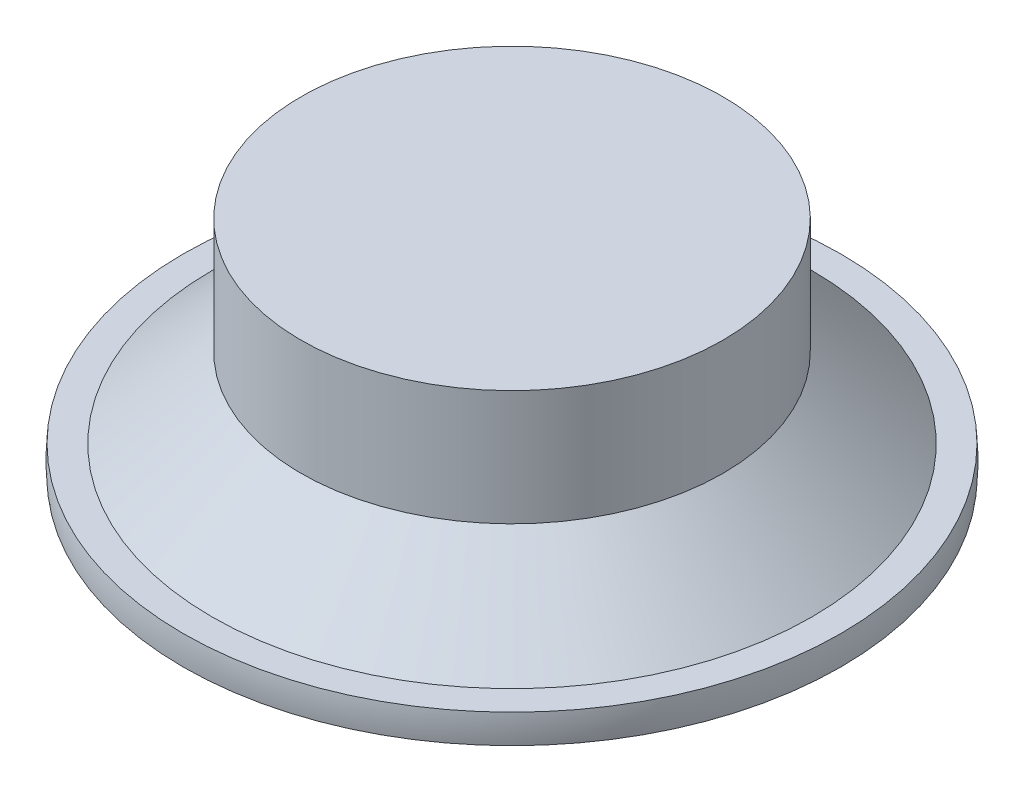
SolidWorks part; units mm, degrees
ref_plane "Plan de face" through (0, 0, 0) normal (0, 0, 1) x (1, 0, 0)
ref_plane "Plan de dessus" through (0, 0, 0) normal (0, 1, 0) x (1, 0, 0)
ref_plane "Plan de droite" through (0, 0, 0) normal (1, 0, 0) x (0, 0, -1)
sketch "Esquisse1" plane through (0, 0, 0) normal (0, 0, 1) x (1, 0, 0)
  line L0 (0, 21.4094) -> (0, 27.2)
  line L1 (0, -43.0328) -> (0, 43.0328) construction
  line L2 (0, 27.2) -> (25.6, 27.2)
  line L3 (25.6, 27.2) -> (25.6, 13.2)
  line L4 (39.9054, 3.52) -> (36.4054, 3.52)
  line L5 (36.4054, 3.52) -> (25.6, 13.2)
  line L6 (22, 0) -> (-22, 0) construction
  line L7 (39.9054, 0) -> (0, 0)
  line L8 (0, 0) -> (0, 27.2)
  line L9 (40, 1.76) -> (40, 0) construction
  line L10 (40, 0) -> (40, -1.4062) construction
  line L11 (0, 27.2) -> (0, 0)
  arc A0 (39.9054, 0) -> (39.9054, 3.52) centre (23.5754, 1.76) ccw
  dimension "D1" = 27.2
  dimension "D2" = 40
  dimension "D3" = 25.6
  dimension "D4" = 3.52
  dimension "D5" = 14
  dimension "D6" = 3.5
revolve "Révolution2" add sketch "Esquisse1" angle 360 about L8 region at (15.138, 12.4022, 0)
